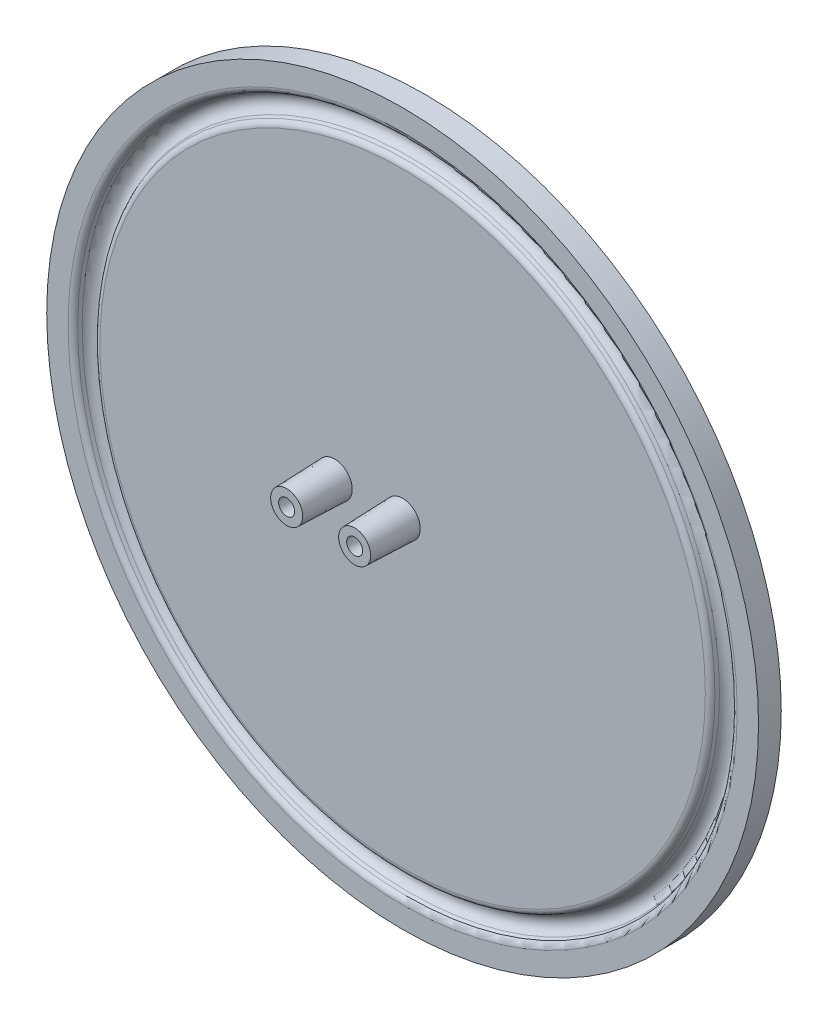
SolidWorks part; units mm, degrees
ref_plane "Front Plane" through (0, 0, 0) normal (0, 0, 1) x (1, 0, 0)
ref_plane "Top Plane" through (0, 0, 0) normal (0, 1, 0) x (1, 0, 0)
ref_plane "Right Plane" through (0, 0, 0) normal (1, 0, 0) x (0, 0, -1)
sketch "Sketch1" plane through (0, 0, 0) normal (1, 0, 0) x (0, 0, -1)
  line L0 (0, 0) -> (7.9248, 0) construction
  line L1 (0, 0) -> (0, 37.8485)
  line L2 (0, 44.5) -> (2.8448, 44.5)
  line L3 (2.8448, 44.5) -> (7.9248, 37.245)
  line L4 (7.9248, 37.245) -> (7.9248, 0)
  line L5 (0, 41.8297) -> (0, 44.5)
  line L6 (0.4797, 41.1049) -> (0.8729, 40.938)
  line L7 (0.4797, 38.5733) -> (0.8729, 38.7402)
  line L8 (0, 41.3085) -> (0, 38.3697) construction
  line L9 (0, 39.8391) -> (0.4064, 39.8391) construction
  line L10 (0, 0) -> (7.9248, 0)
  arc A0 (0.8729, 38.7402) -> (0.8729, 40.938) centre (0.4064, 39.8391) ccw
  arc A2 (0, 37.8485) -> (0.4797, 38.5733) centre (0.7874, 37.8485) cw
  arc A3 (0, 41.8297) -> (0.4797, 41.1049) centre (0.7874, 41.8297) ccw
revolve "Revolve1" add sketch "Sketch1" angle 360 about L0
sketch "Sketch2" plane through (0, 0, -7.9248) normal (0, 0, -1) x (-1, 0, 0)
  circle A1 centre (-8.5, 0) radius 2.2
  circle A2 centre (0, 0) radius 2.2
  circle A3 centre (8.5, 0) radius 2.2
  dimension "D1" = 4.4
  dimension "D2" = 4.4
  dimension "D3" = 4.4
  dimension "D4" = 8.5
  dimension "D5" = 8.5
ref_plane "Plane1" through (0, 0, -13.9248) normal (0, 0, -1) x (-1, 0, 0)
sketch "Sketch3" plane through (0, 0, -13.9248) normal (0, 0, -1) x (-1, 0, 0)
  circle A0 centre (-8.5, 0) radius 2
  circle A1 centre (0, 0) radius 2
  circle A2 centre (8.5, 0) radius 2
  dimension "D1" = 4
  dimension "D2" = 4
  dimension "D3" = 4
loft "Loft1" add section "Sketch2" section "Sketch3" connector at (7.7366, -2.0633, -7.9248) connector at (7.8242, -1.8824, -13.9248)
loft "Loft2" add section "Sketch2<5>" section "Sketch3<5>" connector at (-1.4214, -1.6792, -7.9248) connector at (-1.3116, -1.5098, -13.9248)
sketch "Sketch2<5>" plane through (0, 0, -7.9248) normal (0, 0, -1) x (-1, 0, 0) same geometry as "Sketch2"
sketch "Sketch3<5>" plane through (0, 0, -13.9248) normal (0, 0, -1) x (-1, 0, 0) same geometry as "Sketch3"
loft "Loft3" add section "Sketch2<6>" section "Sketch3<6>" connector at (-7.7496, -2.0681, -7.9248) connector at (-8.0442, -1.9474, -13.9248)
sketch "Sketch2<6>" plane through (0, 0, -7.9248) normal (0, 0, -1) x (-1, 0, 0) same geometry as "Sketch2"
sketch "Sketch3<6>" plane through (0, 0, -13.9248) normal (0, 0, -1) x (-1, 0, 0) same geometry as "Sketch3"
shell "Shell2" thickness 1 removed face at (6.5, 0, -13.9248)
shell "Shell3" thickness 1 removed face at (-2, 0, -13.9248)
shell "Shell4" thickness 1 removed face at (-10.5, 0, -13.9248)
ref_plane "Plane2" through (0, 0, -3.9624) normal (0, 0, -1) x (-1, 0, 0)
mirror "Mirror4" about plane through (0, 0, -3.9624) normal (0, 0, -1) of bodies 109 110
sketch "Sketch4" plane through (0, 0, -8.9248) normal (0, 0, -1) x (-1, 0, 0)
  circle A0 centre (0, 0) radius 1.1661
  circle A1 centre (8.5, 0) radius 1.1661
extrude "Cut-Extrude2" cut sketch "Sketch4" against normal up to surface (9.9248 mm away) up to face at (-1.1661, 0, 1)
equation "\"D2@Sketch2\"=\"D1@Sketch2\""
equation "\"D3@Sketch2\"=\"D1@Sketch2\""
equation "\"D2@Sketch3\"=\"D1@Sketch3\""
equation "\"D3@Sketch3\"=\"D1@Sketch3\""
equation "\"B@Sketch1\"=\"A@Sketch1\"-9.3218"
